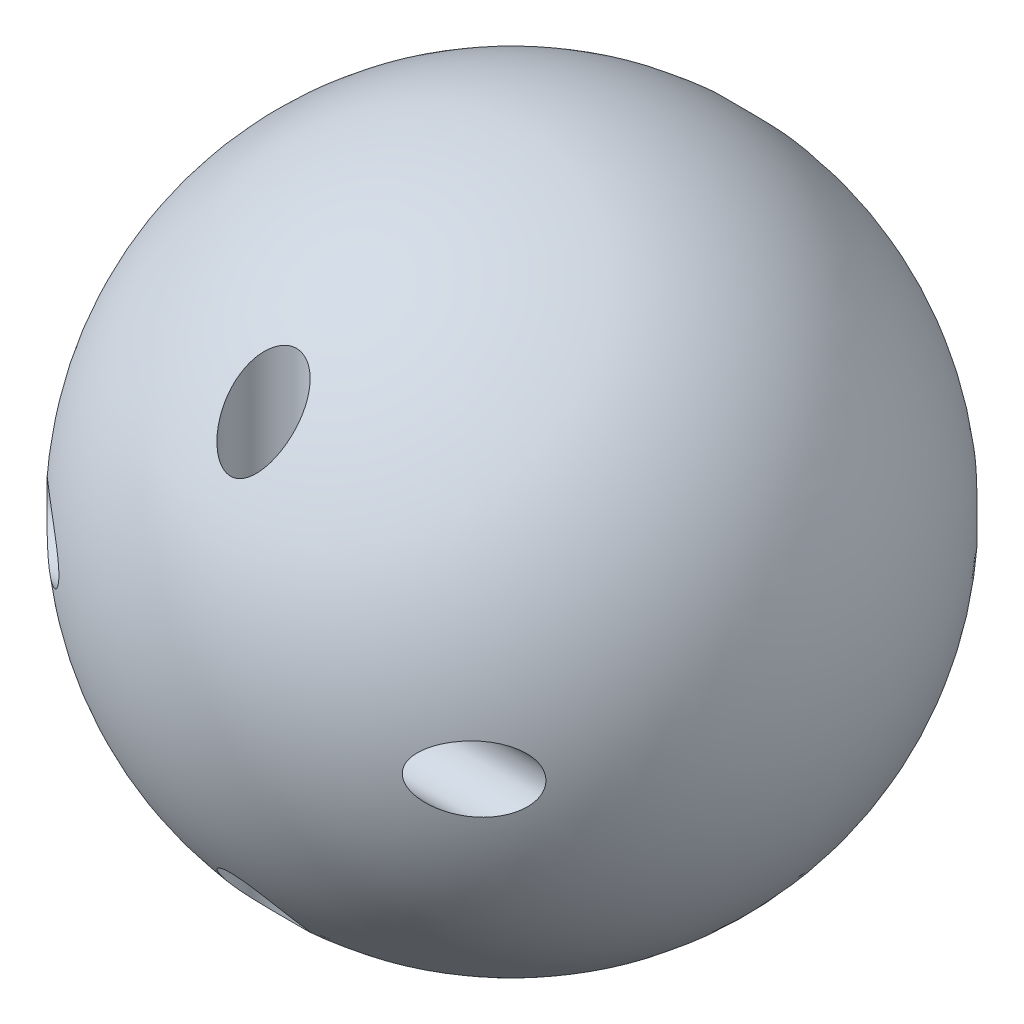
SolidWorks part; units mm, degrees
ref_plane "Front" through (0, 0, 0) normal (0, 0, 1) x (1, 0, 0)
ref_plane "Top" through (0, 0, 0) normal (0, 1, 0) x (1, 0, 0)
ref_plane "Right" through (0, 0, 0) normal (1, 0, 0) x (0, 0, -1)
sketch "Croquis2" plane through (0, 0, 0) normal (0, 0, 1) x (1, 0, 0)
  line L0 (0, 9.2847) -> (0, -9.2847)
  line L1 (0, 0) -> (0, 14.5467) construction
  arc A0 (0, 9.2847) -> (0, -9.2847) centre (0, 0) cw
revolve "Revolución3" add sketch "Croquis2" angle 360 about L1
sketch "Croquis3" plane through (0, 0, 0) normal (0, 1, 0) x (1, 0, 0)
  line L0 (0, 0) -> (9.0002, 0) construction
  circle A0 centre (0, 6.9979) radius 0.9281
  circle A1 centre (0, -6.9979) radius 0.9281
extrude "Cortar-Extruir1" cut sketch "Croquis3" against normal blind 11 and the other way blind 10
sketch "Croquis4" plane through (0, 0, 0) normal (1, 0, 0) x (0, 0, -1)
  line L0 (7.9261, -4.8356) -> (7.9261, 4.8356) construction
  line L1 (6.0698, 7.0258) -> (6.0698, -7.0259) construction
  line L2 (0, 0) -> (0, -7.73) construction
  circle A0 centre (6.9979, 0) radius 0.9281
  circle A1 centre (-6.9979, 0) radius 0.9281
extrude "Cortar-Extruir2" cut sketch "Croquis4" against normal blind 11 and the other way blind 11
sketch "Croquis6" plane through (0, 0, 0) normal (0, 0, 1) x (1, 0, 0)
  circle A0 centre (0, 0) radius 2.7487
extrude "Saliente-Extruir1" add sketch "Croquis6" along normal blind 8 and the other way blind 8 contours A0
